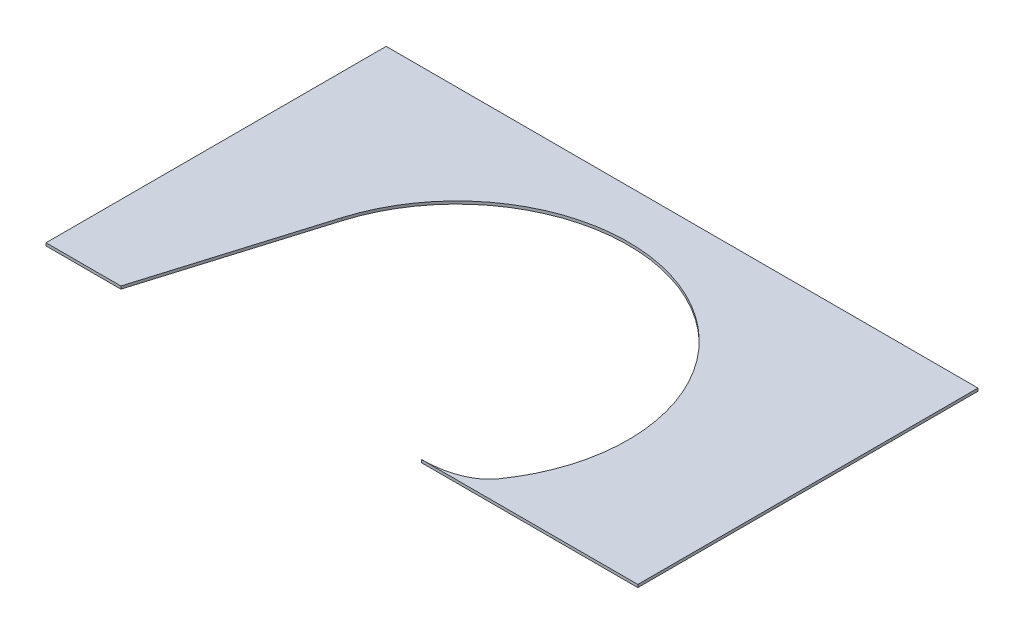
SolidWorks part; units mm, degrees
ref_plane "Front Plane" through (0, 0, 0) normal (0, 0, 1) x (1, 0, 0)
ref_plane "Top Plane" through (0, 0, 0) normal (0, 1, 0) x (1, 0, 0)
ref_plane "Right Plane" through (0, 0, 0) normal (1, 0, 0) x (0, 0, -1)
sketch "Sketch1" plane through (0, 0, 0) normal (0, 1, 0) x (1, 0, 0)
  line L1 (0, 0) -> (679.45, 0)
  line L2 (0, 0) -> (0, 390.525)
  line L3 (0, 390.525) -> (679.45, 390.525)
  line L4 (679.45, 0) -> (679.45, 390.525)
  dimension "D1" = 679.45
  dimension "D2" = 390.525
extrude "Boss-Extrude1" add sketch "Sketch1" along normal blind 3.175
sketch "Sketch2" plane through (0, 3.175, 0) normal (0, 1, 0) x (1, 0, 0)
  line L12 (85.9696, 0) -> (144.9431, 195.1259)
  line L13 (0, 0) -> (679.45, 0) construction
  line L14 (85.9696, 0) -> (431.2404, 0)
  arc A8 (494.6251, 25.267) -> (530.1226, 131.8255) centre (333.375, 138.1755) ccw construction
  arc A10 (327.025, 334.9231) -> (144.9431, 195.1259) centre (333.375, 138.1755) ccw construction
  arc A11 (530.1226, 131.8255) -> (327.025, 334.9231) centre (333.375, 138.1755) ccw construction
  arc A12 (494.6251, 25.267) -> (530.1226, 131.8255) centre (333.375, 138.1755) ccw
  arc A14 (327.025, 334.9231) -> (144.9431, 195.1259) centre (333.375, 138.1755) ccw
  arc A15 (530.1226, 131.8255) -> (327.025, 334.9231) centre (333.375, 138.1755) ccw
  spline S0 degree 3 poles (579.0964, 1021.6913) (461.012, 179.8327) (536.0415, 62.5716) (484.7792, 14.7499) (475.3357, 8.7521) (461.5217, 3.5394) (336.0356, -21.0091) (128.9981, 153.0165) (1337.1517, 423.4672) knots -0.818542 -0.818542 -0.818542 -0.818542 0.027722 0.055445 0.110889 0.166334 0.221779 1.450191 1.450191 1.450191 1.450191 only from (494.6251, 25.267) to (431.2444, 0) construction
  spline S1 degree 3 poles (494.6251, 25.267) (493.4573, 23.5992) (490.8952, 20.4555) (484.7792, 14.7499) (475.3357, 8.7521) (461.5217, 3.5394) (446.5259, 0.6059) (436.1491, 0) (431.2404, 0) knots 0 0 0 0 0.027722 0.055445 0.110889 0.166334 0.221779 0.270938 0.270938 0.270938 0.270938
  dimension "D1" = 196.85
extrude "Cut-Extrude1" cut sketch "Sketch2" against normal through all
